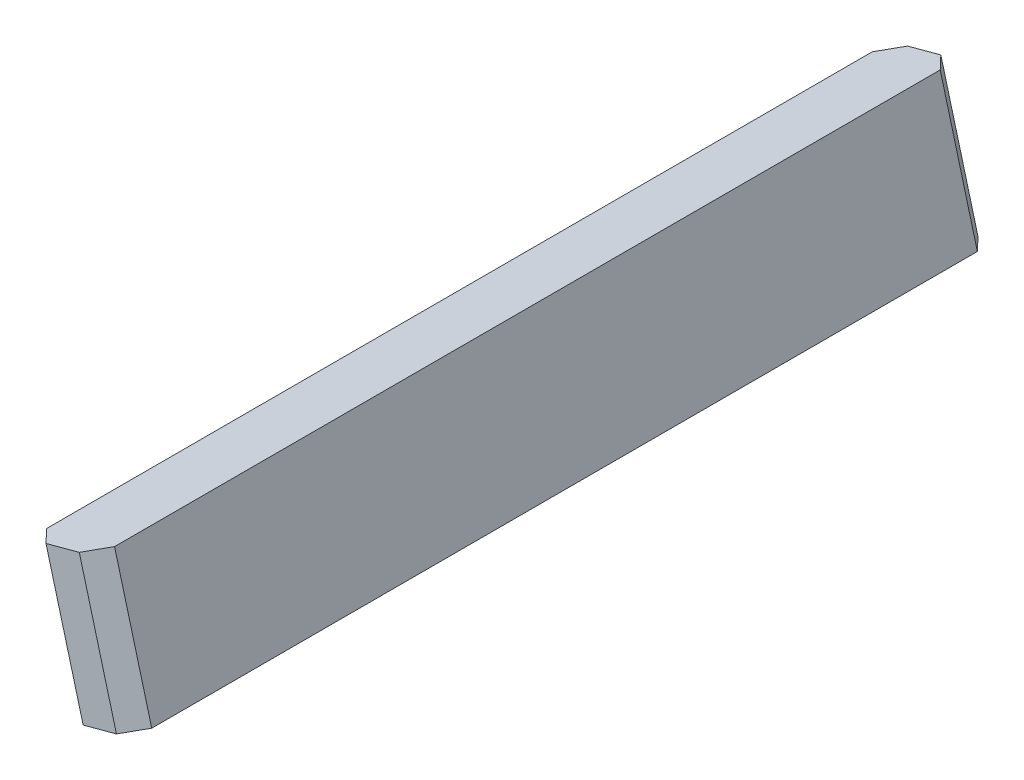
SolidWorks part; units mm, degrees
ref_plane "Front Plane" through (0, 0, 0) normal (0, 0, 1) x (1, 0, 0)
ref_plane "Top Plane" through (0, 0, 0) normal (0, 1, 0) x (1, 0, 0)
ref_plane "Right Plane" through (0, 0, 0) normal (1, 0, 0) x (0, 0, -1)
sketch "Sketch1" plane through (0, 0, 0) normal (0, 0, 1) x (1, 0, 0)
  line L0 (0, 0) -> (0, 38.637) construction
  line L1 (0, 38.637) -> (10.3528, 0)
  line L2 (10.3528, 0) -> (20.0089, 2.6)
  line L3 (20.0089, 2.6) -> (10.3528, 38.637)
  line L4 (0, 38.637) -> (10.3528, 38.637)
  dimension "D1" = 10
  dimension "D2" = 15
  dimension "D3" = 40
  dimension "D4" = 2.6
extrude "Boss-Extrude1" add sketch "Sketch1" along normal mid plane 120 contours L3 L4 L1 L2
sketch "Sketch2" plane through (0, 0, 60) normal (0, 0, 1) x (1, 0, 0)
  line L0 (5.1764, 19.3185) -> (14.8325, 21.9185)
  line L1 (0, 38.637) -> (10.3528, 0) construction
  line L2 (20.0089, 2.6) -> (10.3528, 38.637) construction
  line L3 (10.3528, 0) -> (20.0089, 2.6) construction
  line L4 (14.8325, 21.9185) -> (10.3528, 38.637)
  line L5 (10.3528, 38.637) -> (0, 38.637)
  line L6 (0, 38.637) -> (5.1764, 19.3185)
extrude "Cut-Extrude1" cut sketch "Sketch2" against normal through all contours L0 L4 L5 L6
other "Move Face1" flip direction yes face at (17.4207, 12.2593, 0) face at (7.7646, 9.6593, 0) offset 0.1 parameters "D1"=0.1
chamfer "Chamfer1" distance 2.5 angle 45 4 edges at (17.3241, 12.2333, 60) (7.8611, 9.6853, 60) (17.3241, 12.2333, -60) (7.8611, 9.6853, -60)
